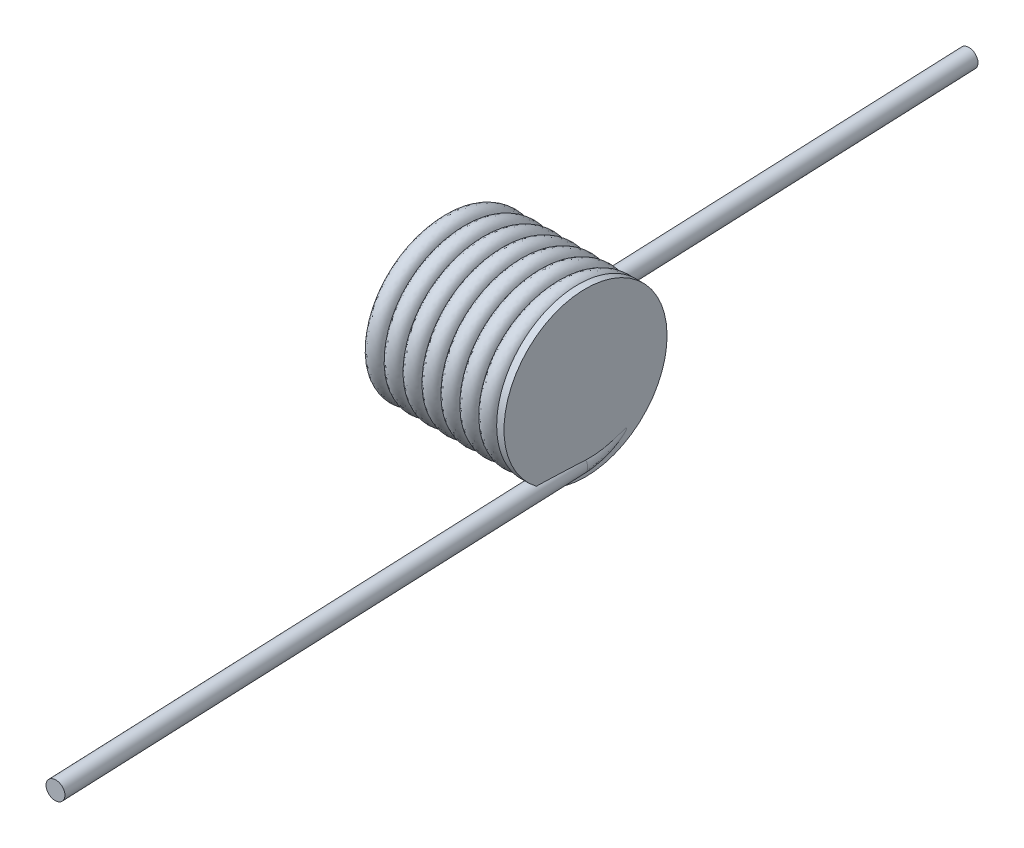
SolidWorks part; units mm, degrees
ref_plane "Front" through (0, 0, 0) normal (0, 0, 1) x (1, 0, 0)
ref_plane "Top" through (0, 0, 0) normal (0, 1, 0) x (1, 0, 0)
ref_plane "Right" through (0, 0, 0) normal (1, 0, 0) x (0, 0, -1)
sketch "Sketch1" plane through (0, 0, 0) normal (1, 0, 0) x (0, 0, -1)
  line L0 (0, -2.2098) -> (0, -2.8448) construction
  line L1 (0, -2.8448) -> (19.05, -2.8448) construction
  line L2 (0, -2.8448) -> (-19.05, -2.8448) construction
  line L3 (0, 0) -> (2.8448, 0) construction
  line L4 (0, 0) -> (0, -2.8448) construction
  line L5 (-19.05, -2.8448) -> (-19.05, -2.2098) construction
  line L6 (-19.05, -2.2098) -> (0, -2.2098) construction
  line L7 (19.05, -2.8448) -> (19.05, -2.2098) construction
  line L8 (19.05, -2.2098) -> (0, -2.2098) construction
  circle A0 centre (0, 0) radius 2.8448 construction
  circle A1 centre (0, 0) radius 1.778 construction
  circle A2 centre (0, 0) radius 2.5273 construction
  point P7 (0, -2.5273)
  point P10 (0, 2.8448)
  dimension "OD" = 5.6896
  dimension "For Shaft Diameter" = 3.556
  dimension "Wire Diameter" = 0.635
  dimension "Leg Length" = 19.05
  dimension "Deflection Angle" = 180
sketch "Sketch2" plane through (0, 0, 0) normal (1, 0, 0) x (0, 0, -1)
  circle A0 centre (0, 0) radius 2.5273 construction
  circle A2 centre (0, 0) radius 2.5273
curve "Helix/Spiral1" pitch 0.6604 height 4.6228 radius 2.5273 left hand yes centre (0, 0, 0) axis (-1, 0, 0) start towards (0, 0, -1)
ref_plane "Plane1" through (0, -2.5273, 0) normal (-0.0416, 0, -0.9991) x (0.9989, -0.0232, -0.0415)
sketch "Sketch3" plane through (0, -2.5273, 0) normal (-0.0416, 0, -0.9991) x (0.9989, -0.0232, -0.0415)
  circle A0 centre (0, 0) radius 0.3175
  dimension "D1" = 0.635
sweep "Sweep1" add profiles "Sketch3" path "Helix/Spiral1"
sketch "Sketch4" plane through (0, 0, 0) normal (0.0416, 0, 0.9991) x (-0.9989, 0.0232, 0.0415)
  circle A1 centre (-0.0587, 2.5266) radius 0.3175
  circle A2 centre (-0.0587, 2.5266) radius 0.3175
  dimension "D1" = 0
extrude "Extrude1" add sketch "Sketch4" along normal blind 19.05
sketch "Sketch5" plane through (-0.008, 0, -0.1919) normal (-0.0416, 0, -0.9991) x (0.9979, 0.0499, -0.0415)
  circle A1 centre (-4.7392, 2.2935) radius 0.3175
  circle A2 centre (-4.7392, 2.2935) radius 0.3175
  dimension "D1" = 0
extrude "Extrude2" add sketch "Sketch5" along normal blind 19.05
sketch "Sketch6" plane through (0, 0, 0) normal (1, 0, 0) x (0, 0, -1)
  circle A2 centre (0, 0) radius 2.2098 construction
sketch "Sketch7" plane through (0, 0, 0) normal (1, 0, 0) x (0, 0, -1)
  circle A1 centre (0, 0) radius 2.8448
  dimension "D1" = 5.6896
extrude "Boss-Extrude1" add sketch "Sketch7" along normal blind 0.254
equation "\"D4@Helix/Spiral1\" = \"Wire Diameter@Sketch1\" + .001"
equation "\"D1@Sketch3\"=\"Wire Diameter@Sketch1\""
equation "\"D1@Extrude2\"=\"Leg Length@Sketch1\""
equation "\"Leg Length@Extrude1\"=\"Leg Length@Sketch1\""
